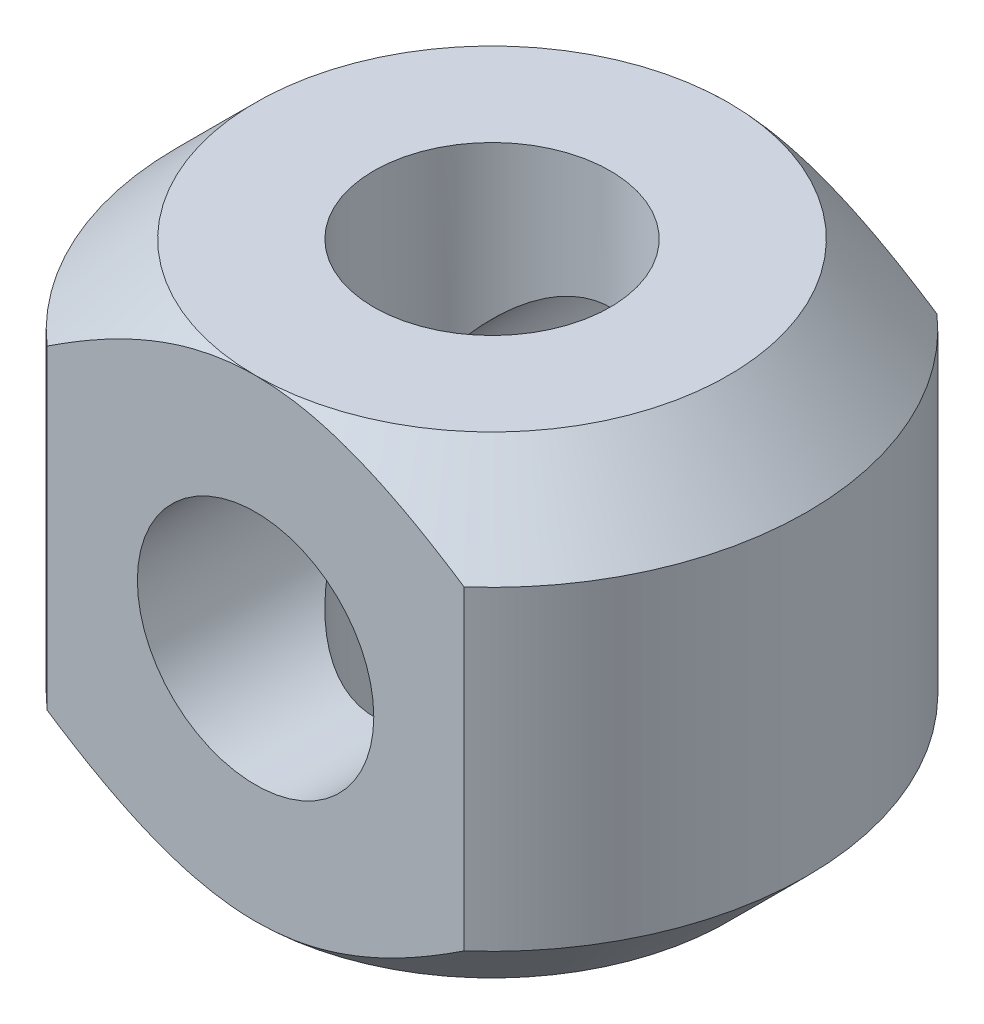
SolidWorks part; units mm, degrees
ref_plane "Alzado" through (0, 0, 0) normal (0, 0, 1) x (1, 0, 0)
ref_plane "Planta" through (0, 0, 0) normal (0, 1, 0) x (1, 0, 0)
ref_plane "Vista lateral" through (0, 0, 0) normal (1, 0, 0) x (0, 0, -1)
sketch "Croquis1" plane through (0, 0, 0) normal (0, 1, 0) x (1, 0, 0)
  circle A0 centre (0, 0) radius 4
  circle A1 centre (0, 0) radius 1.5
  dimension "D1" = 8
  dimension "D2" = 3
extrude "Saliente-Extruir3" add sketch "Croquis1" along normal blind 6
chamfer "Chaflán1" distance 1 angle 45 1 edges at (0, 6, 4)
chamfer "Chaflán2" distance 1 angle 45 1 edges at (0, 0, 4)
sketch "Croquis3" plane through (0, 0, 0) normal (1, 0, 0) x (0, 0, -1)
  line L0 (-4, 5) -> (-4, 1) construction
  line L1 (-5, 0) -> (-3, 0)
  line L2 (-5, 0) -> (-5, 6)
  line L3 (-5, 6) -> (-3, 6)
  line L4 (-3, 0) -> (-3, 6)
  line L5 (-5, 0) -> (-3, 6) construction
  line L6 (-5, 6) -> (-3, 0) construction
  line L7 (4, 1) -> (4, 5) construction
  line L8 (3, 0) -> (5, 0)
  line L9 (3, 0) -> (3, 6)
  line L10 (3, 6) -> (5, 6)
  line L11 (5, 0) -> (5, 6)
  line L12 (3, 0) -> (5, 6) construction
  line L13 (3, 6) -> (5, 0) construction
  line L14 (-4, 5) -> (-4, 1) construction
  point P0 (-4, 3)
  point P7 (4, 3)
  dimension "D1" = 6
  dimension "D2" = 1
  dimension "D3" = 6
  dimension "D4" = 6
extrude "Cortar-Extruir2" cut sketch "Croquis3" against normal blind 4 and the other way blind 4
sketch "Croquis4" plane through (0, 0, 3) normal (0, 0, 1) x (1, 0, 0)
  line L0 (0, 0) -> (0, 6) construction
  circle A0 centre (0, 3) radius 1.5
  dimension "D1" = 3
extrude "Cortar-Extruir3" cut sketch "Croquis4" against normal blind 6
